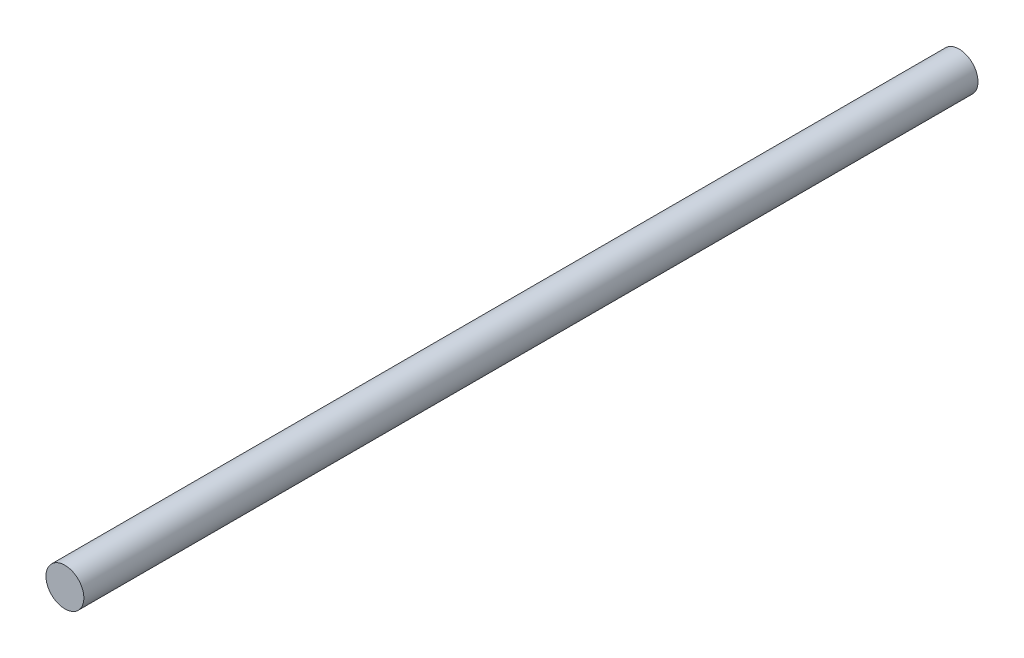
SolidWorks part; units mm, degrees
material "AISI Acero para herramientas tipo A2"
ref_plane "Alzado" through (0, 0, 0) normal (0, 0, 1) x (1, 0, 0)
ref_plane "Planta" through (0, 0, 0) normal (0, 1, 0) x (1, 0, 0)
ref_plane "Vista lateral" through (0, 0, 0) normal (1, 0, 0) x (0, 0, -1)
sketch "Croquis1" plane through (0, 0, 0) normal (0, 0, 1) x (1, 0, 0)
  circle A0 centre (0, 0) radius 5
  dimension "D1" = 10
extrude "Saliente-Extruir1" add sketch "Croquis1" along normal blind 236
